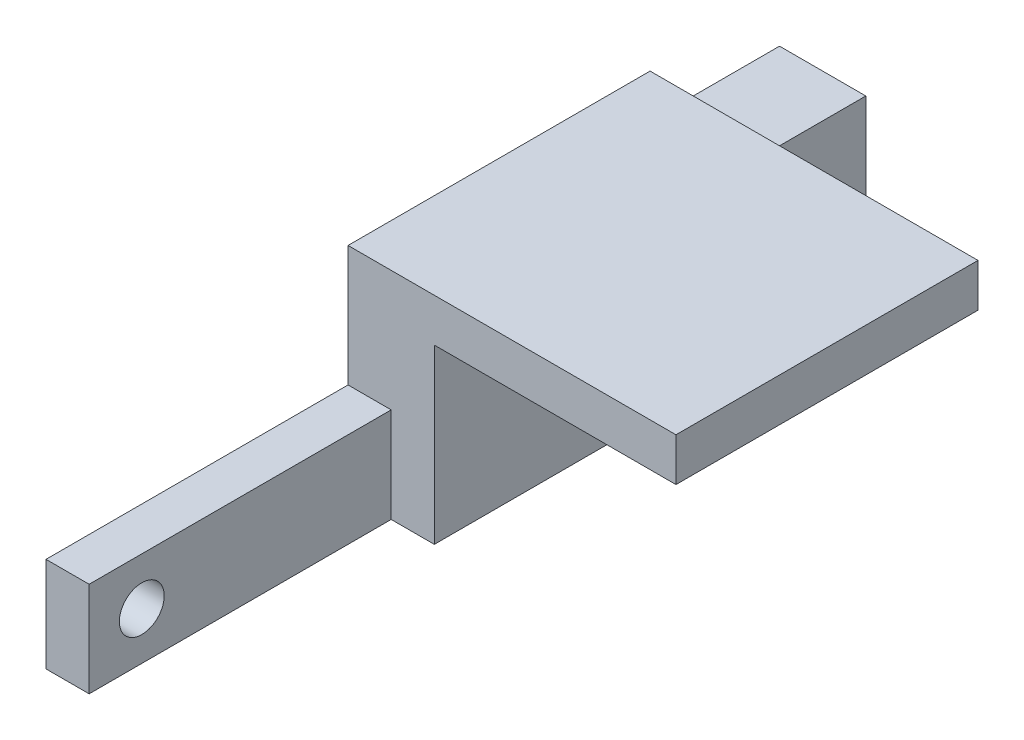
SolidWorks part; units mm, degrees
ref_plane "前视基准面" through (0, 0, 0) normal (0, 0, 1) x (1, 0, 0)
ref_plane "上视基准面" through (0, 0, 0) normal (0, 1, 0) x (1, 0, 0)
ref_plane "右视基准面" through (0, 0, 0) normal (1, 0, 0) x (0, 0, -1)
other "Configuration Table"
sketch "草图1" plane through (0, 0, 0) normal (0, 1, 0) x (1, 0, 0)
  line L5 (38, 0) -> (0, 0)
  line L6 (38, 0) -> (38, -35)
  line L19 (38, -35) -> (0, -35)
  line L20 (0, 0) -> (0, -35)
  line L21 (10, -35) -> (0, -35)
  line L22 (10, -35) -> (10, 15)
  line L23 (10, 15) -> (0, 15)
  line L24 (0, -35) -> (0, 15)
  point P0 (-90.6464, 22.0667)
  dimension "D1" = 35
  dimension "D2" = 38
  dimension "D3" = 10
  dimension "D4" = 50
extrude "凸台-拉伸1" add sketch "草图1" along normal blind 5 contours L5 L20 L19 L6
extrude "凸台-拉伸2" add sketch "草图1<14>" against normal blind 20 contours L23 L24 L21 L22
sketch "草图1<14>" plane through (0, 0, 0) normal (0, 1, 0) x (1, 0, 0) same geometry as "草图1"
sketch "草图2" plane through (10, 0, 0) normal (1, 0, 0) x (0, 0, -1)
  line L0 (-35, 5) -> (-35, -20) construction
  line L1 (-35, -9) -> (-70, -9)
  line L2 (-35, -9) -> (-35, -20)
  line L3 (-35, -20) -> (-70, -20)
  line L4 (-70, -9) -> (-70, -20)
  line L5 (0, 0) -> (15, 0) construction
  line L6 (-35, -20) -> (15, -20) construction
  line L7 (-35, -14.5) -> (-70, -14.5) construction
  circle A1 centre (-67.5, -14.5) radius 0.5
  circle A2 centre (-56.3, -14.5) radius 0.6
  circle A3 centre (-51.4, -14.5) radius 1.5
  circle A5 centre (-63.9, -14.5) radius 2.6
  point P10 (-70, -14.5)
  point P14 (0, 0)
  point P18 (0, 0)
  dimension "D3" = 1
  dimension "D5" = 5.2
  dimension "D7" = 1.2
  dimension "D9" = 3
  dimension "D1" = 35
  dimension "D2" = 14.5
  dimension "D4" = 3.6
  dimension "D6" = 7.6
  dimension "D8" = 4.9
extrude "凸台-拉伸3" add sketch "草图2" against normal up to surface (10 mm away) from offset 5 contours L3 L4 L1 L2 | A5 up to face at (0, -5, 6.6667) offset against normal yes
extrude "切除-拉伸1" cut sketch "草图2<3>" along normal blind 3 from surface contours A2 | A3 starting at face at (0, -6, 22.5)
sketch "草图2<3>" plane through (10, 0, 0) normal (1, 0, 0) x (0, 0, -1) same geometry as "草图2"
